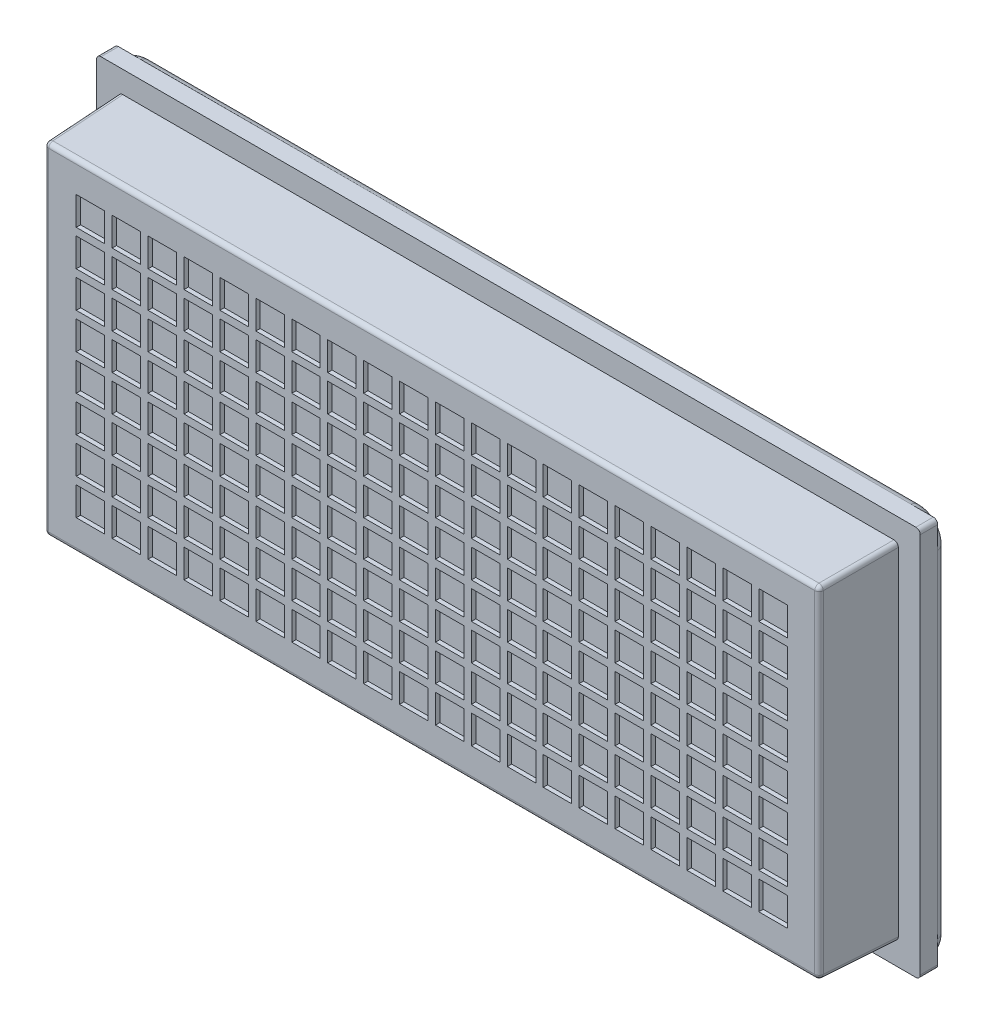
SolidWorks part; units mm, degrees
ref_plane "Front" through (0, 0, 0) normal (0, 0, 1) x (1, 0, 0)
ref_plane "Top" through (0, 0, 0) normal (0, 1, 0) x (1, 0, 0)
ref_plane "Right" through (0, 0, 0) normal (1, 0, 0) x (0, 0, -1)
sketch "Sketch1" plane through (0, 0, 0) normal (0, 0, 1) x (1, 0, 0)
  line L1 (-89, -39.5) -> (89, -39.5)
  line L2 (-89, -39.5) -> (-89, 39.5)
  line L3 (-89, 39.5) -> (89, 39.5)
  line L4 (89, -39.5) -> (89, 39.5)
  line L5 (-89, -39.5) -> (89, 39.5) construction
  line L6 (-89, 39.5) -> (89, -39.5) construction
  point P0 (0, 0)
  dimension "D1" = 178
  dimension "D2" = 79
extrude "Boss-Extrude1" add sketch "Sketch1" along normal blind 17.5 draft 2
fillet "Fillet1" radius 1 4 edges at (88.6944, 39.1944, 8.75) (88.6944, -39.1944, 8.75) (-88.6944, -39.1944, 8.75) (-88.6944, 39.1944, 8.75)
fillet "Fillet2" radius 1 8 edges at (88.0962, 38.5962, 17.5) (88.3889, 0, 17.5) (88.0962, -38.5962, 17.5) (0, -38.8889, 17.5) (-88.0962, -38.5962, 17.5) (-88.3889, 0, 17.5) (-88.0962, 38.5962, 17.5) (0, 38.8889, 17.5)
shell "Shell1" thickness 1 removed face at (0, 0, 0)
sketch "Sketch2" plane through (0, 0, 0) normal (0, 0, -1) x (-1, 0, 0)
  line L0 (87.9994, -38.4994) -> (-87.9994, -38.4994) construction
  line L1 (87.9994, 38.4994) -> (87.9994, -38.4994) construction
  line L2 (-87.9994, -38.4994) -> (-87.9994, 38.4994) construction
  line L3 (-87.9994, 38.4994) -> (87.9994, 38.4994) construction
  line L4 (87.9994, -38.4994) -> (-87.9994, -38.4994)
  line L5 (87.9994, 38.4994) -> (87.9994, -38.4994)
  line L6 (-87.9994, -38.4994) -> (-87.9994, 38.4994)
  line L7 (-87.9994, 38.4994) -> (87.9994, 38.4994)
  line L24 (-88.0006, 39.5) -> (88.0006, 39.5) construction
  line L25 (-93, 44.5) -> (93, 44.5)
  line L26 (-94, 43.5) -> (-94, -43.5)
  line L27 (-93, -44.5) -> (93, -44.5)
  line L28 (94, 43.5) -> (94, -43.5)
  line L29 (-94, 44.5) -> (94, -44.5) construction
  line L30 (-94, -44.5) -> (94, 44.5) construction
  line L32 (-89, -38.5006) -> (-89, 38.5006) construction
  arc A0 (-94, -43.5) -> (-93, -44.5) centre (-93, -43.5) ccw
  arc A1 (93, -44.5) -> (94, -43.5) centre (93, -43.5) ccw
  arc A2 (93, 44.5) -> (94, 43.5) centre (93, 43.5) cw
  arc A3 (-93, 44.5) -> (-94, 43.5) centre (-93, 43.5) ccw
  point P8 (0, 0)
  dimension "D3" = 1
  dimension "D1" = 5
  dimension "D2" = 5
extrude "Boss-Extrude2" add sketch "Sketch2" along normal blind 4
sketch "Sketch5" plane through (0, 0, 17.5) normal (0, 0, 1) x (1, 0, 0)
  line L0 (-87.4232, 38.9226) -> (87.4232, 38.9226) construction
  line L1 (-81.1476, 31.9476) -> (-74.6476, 31.9476)
  line L2 (-81.1476, 31.9476) -> (-81.1476, 25.4476)
  line L3 (-81.1476, 25.4476) -> (-74.6476, 25.4476)
  line L4 (-74.6476, 31.9476) -> (-74.6476, 25.4476)
  line L5 (-88.4226, -37.9232) -> (-88.4226, 37.9232) construction
  dimension "D1" = 6.5
  dimension "D2" = 6.5
  dimension "D3" = 6.975
  dimension "D4" = 7.275
extrude "Cut-Extrude1" cut sketch "Sketch5" against normal through all
pattern_linear "LPattern1" count 20 spacing 8.2 along (1, 0, 0) count 8 spacing 8.2 along (0, -1, 0) of "Cut-Extrude1"
sketch "Sketch4" plane through (0, 0, 16.5) normal (0, 0, -1) x (-1, 0, 0)
  line L1 (-87.4232, 37.9232) -> (87.4232, 37.9232)
  line L2 (-87.4232, 37.9232) -> (-87.4232, -37.9232)
  line L3 (-87.4232, -37.9232) -> (87.4232, -37.9232)
  line L4 (87.4232, 37.9232) -> (87.4232, -37.9232)
extrude "Boss-Extrude3" add sketch "Sketch4" along normal up to vertex (16.5 mm away) draft 2 separate body up to point (87.9994, -38.4994, 0) draft outward yes
sketch "Sketch8" plane through (0, 0, 0) normal (0, 0, -1) x (-1, 0, 0)
  line L1 (-87.9994, 38.4994) -> (87.9994, 38.4994)
  line L2 (-87.9994, 38.4994) -> (-87.9994, -38.4994)
  line L3 (-87.9994, -38.4994) -> (87.9994, -38.4994)
  line L4 (87.9994, 38.4994) -> (87.9994, -38.4994)
sketch "Sketch6" plane through (0, 0, 0) normal (1, 0, 0) x (0, 0, -1)
  line L0 (4, 38.4994) -> (4, 44.5)
  line L2 (4, 43.5) -> (4, -43.5) construction
  line L3 (4, 43.5) -> (4, 44.5) construction
  line L4 (4, 44.5) -> (0, 44.5) construction
  arc A2 (4, 44.5) -> (4, 38.4994) centre (3.4496, 41.4997) cw
  dimension "D1" = 2.5
sketch "Sketch7" plane through (0, 0, -4) normal (0, 0, -1) x (-1, 0, 0)
  line L0 (87.9994, 38.4994) -> (87.9994, -38.4994) construction
  line L1 (87.9994, -38.4994) -> (-87.9994, -38.4994) construction
  line L2 (-87.9994, -38.4994) -> (-87.9994, 38.4994) construction
  line L3 (-87.9994, 38.4994) -> (87.9994, 38.4994) construction
  line L4 (87.9994, 38.3994) -> (87.9994, -38.3994)
  line L5 (87.8994, -38.4994) -> (-87.8994, -38.4994)
  line L6 (-87.9994, -38.3994) -> (-87.9994, 38.3994)
  line L7 (-87.8994, 38.4994) -> (87.8994, 38.4994)
  arc A0 (-87.9994, 38.3994) -> (-87.8994, 38.4994) centre (-87.8994, 38.3994) cw
  arc A1 (-87.8994, -38.4994) -> (-87.9994, -38.3994) centre (-87.8994, -38.3994) cw
  arc A2 (87.9994, -38.3994) -> (87.8994, -38.4994) centre (87.8994, -38.3994) cw
  arc A3 (87.9994, 38.3994) -> (87.8994, 38.4994) centre (87.8994, 38.3994) ccw
  dimension "D1" = 0.1
extrude "Boss-Extrude5" add sketch "Sketch8" along normal up to surface (4 mm away) separate body up to face at (0, 0, -4)
sweep "Sweep4" add profiles "Sketch6" path "Sketch7"
